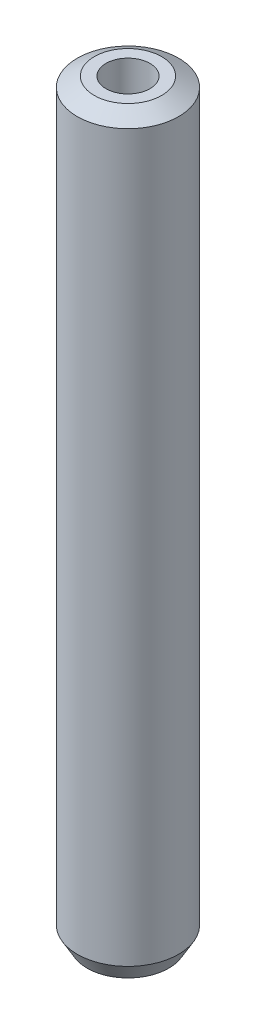
SolidWorks part; units mm, degrees
ref_plane "Front Plane" through (0, 0, 0) normal (0, 0, 1) x (1, 0, 0)
ref_plane "Top Plane" through (0, 0, 0) normal (0, 1, 0) x (1, 0, 0)
ref_plane "Right Plane" through (0, 0, 0) normal (1, 0, 0) x (0, 0, -1)
sketch "Sketch1" plane through (0, 0, 0) normal (0, 1, 0) x (1, 0, 0)
  circle A0 centre (0, 0) radius 5
  dimension "SHAFT_OD" = 10
extrude "Boss-Extrude1" add sketch "Sketch1" along normal blind 74.2343
sketch "Sketch2" plane through (0, 0, 0) normal (0, 1, 0) x (1, 0, 0)
  circle A0 centre (0, 0) radius 2.1682
  dimension "BORE_D" = 4.3364
extrude "Cut-Extrude1" cut sketch "Sketch2" along normal through all
chamfer "Chamfer1" distance 0.9675 angle 60 2 edges at (0, 74.2343, 5) (0, 0, 5) first distance on face at (0, 74.2343, 5) first distance on face at (0, 0, 2.1682)
